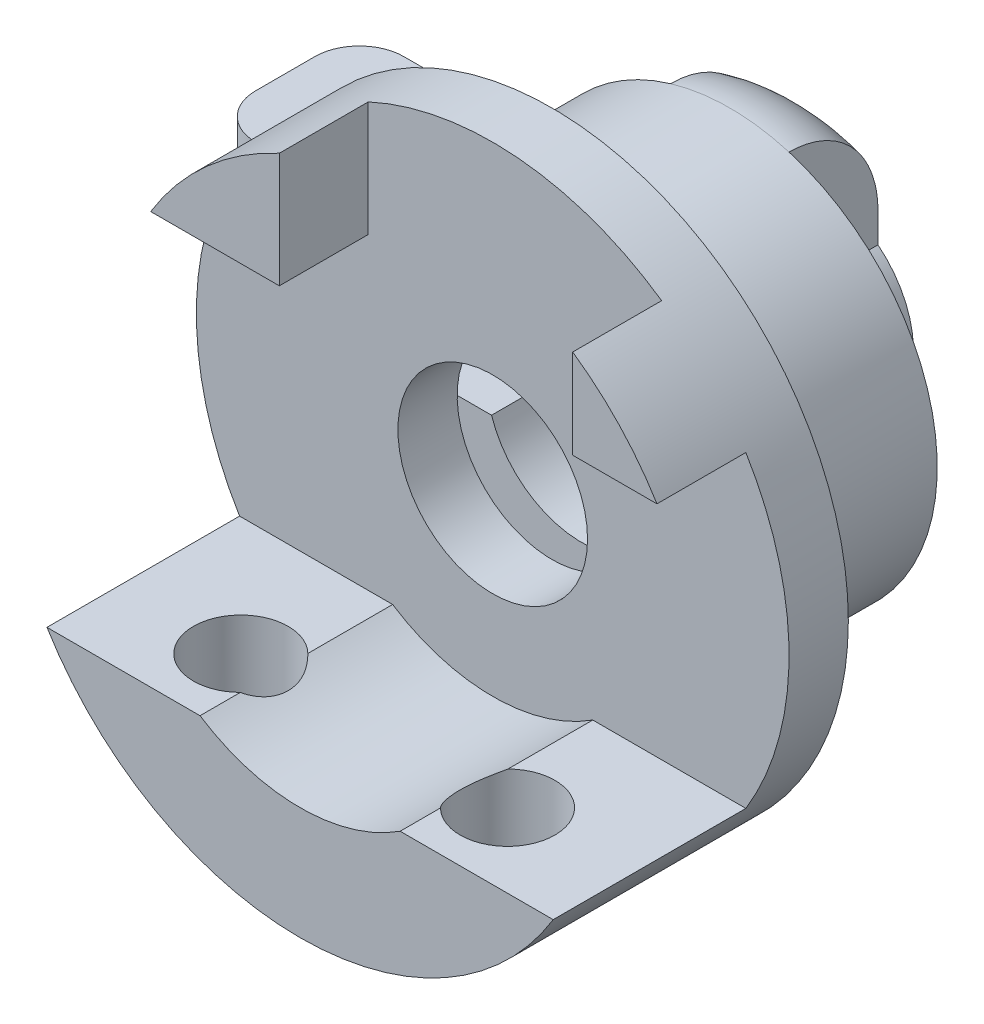
SolidWorks part; units mm, degrees
ref_plane "前视基准面" through (0, 0, 0) normal (0, 0, 1) x (1, 0, 0)
ref_plane "上视基准面" through (0, 0, 0) normal (0, 1, 0) x (1, 0, 0)
ref_plane "右视基准面" through (0, 0, 0) normal (1, 0, 0) x (0, 0, -1)
sketch "草图1" plane through (0, 0, 0) normal (0, 0, 1) x (1, 0, 0)
  circle A0 centre (0, 0) radius 10
extrude "凸台-拉伸1" add sketch "草图1" along normal blind 2
sketch "草图2" plane through (0, 0, 2) normal (0, 0, 1) x (1, 0, 0)
  line L0 (3.3764, -5.2) -> (8.5417, -5.2)
  line L1 (-4.2, 5.2) -> (-8.5417, 5.2)
  line L2 (-3.3764, -5.2) -> (-8.5417, -5.2)
  line L3 (-4.2, 5.2) -> (-4.2, 9.0752)
  line L4 (5.7, 5.2) -> (8.5417, 5.2)
  line L5 (5.7, 5.2) -> (5.7, 8.2164)
  circle A0 centre (0, 0) radius 10 construction
  arc A2 (-3.3764, -5.2) -> (3.3764, -5.2) centre (0, 0) ccw
  arc A4 (-4.2, 9.0752) -> (-8.5417, 5.2) centre (0, 0) ccw
  arc A5 (5.7, 8.2164) -> (8.5417, 5.2) centre (0, 0) cw
  arc A6 (-8.5417, -5.2) -> (-4.3589, -9) centre (0, 0) ccw
  arc A7 (8.5417, -5.2) -> (3.5784, -9.3378) centre (0, 0) cw
  arc A8 (-4.3589, -9) -> (3.5784, -9.3378) centre (0, 0) ccw
  point P3 (0, 0)
extrude "凸台-拉伸2" add sketch "草图2" along normal blind 3
sketch "草图3" plane through (0, 0, 2) normal (0, 0, 1) x (1, 0, 0)
  circle A0 centre (0, 0) radius 3.2
extrude "切除-拉伸1" cut sketch "草图3" against normal blind 3
sketch "草图5" plane through (0, 0, 0) normal (0, 0, -1) x (-1, 0, 0)
  line L0 (-3.5, 6.0622) -> (-3.5, 3.2)
  line L1 (-3.5, 3.2) -> (3.5, 3.2)
  line L5 (3.5, 6.0622) -> (3.5, 3.2)
  arc A1 (-3.5, 6.0622) -> (3.5, 6.0622) centre (0, 0) cw
  point P8 (0, 3.2)
extrude "凸台-拉伸3" add sketch "草图5" along normal blind 1
sketch "草图6" plane through (0, 0, -1) normal (0, 0, -1) x (-1, 0, 0)
  circle A0 centre (0, 0) radius 3.2
  circle A2 centre (0, 0) radius 7
extrude "凸台-拉伸4" add sketch "草图6" along normal blind 5
sketch "草图7" plane through (0, 0, -6) normal (0, 0, -1) x (-1, 0, 0)
  line L4 (12.5, -3) -> (12.5, 3)
  line L5 (4.4372, 3) -> (4.4372, -3)
  line L6 (12.5, 3) -> (4.4372, 3)
  line L7 (12.5, -3) -> (4.4372, -3)
extrude "凸台-拉伸5" add sketch "草图7" against normal blind 5
sketch "草图8" plane through (0, 3, 0) normal (0, 1, 0) x (1, 0, 0)
  circle A0 centre (-9.5, 3.5) radius 1.5
extrude "切除-拉伸3" cut sketch "草图8" against normal through all
sketch "草图9" plane through (0, 0, -6) normal (0, 0, -1) x (-1, 0, 0)
  line L0 (0, 0) -> (0, 1)
  line L1 (0, 1) -> (12.5, 1)
  line L2 (12.5, -3) -> (12.5, 3) construction
  line L3 (0, 0) -> (0, -1)
  line L4 (0, -1) -> (12.5, -1)
  line L5 (12.5, -1) -> (12.5, 1)
extrude "切除-拉伸4" cut sketch "草图9" against normal blind 5
fillet "圆角7" radius 1.5 4 edges at (-12.5, -2, -6) (-12.5, -2, -1) (-12.5, 2, -1) (-12.5, 2, -6)
sketch "草图10" plane through (0, 0, -6) normal (0, 0, -1) x (-1, 0, 0)
  line L5 (2, 6.7082) -> (2, 2.498)
  line L6 (-2, 6.7082) -> (-2, 2.498)
  arc A0 (-2, 2.498) -> (2, 2.498) centre (0, 0) cw
  circle A1 centre (0, 0) radius 3.2 construction
  arc A2 (2, 6.7082) -> (-2, 6.7082) centre (0, 0) ccw
  arc A3 (3.5, 6.0622) -> (-3.5, 6.0622) centre (0, 0) ccw construction
extrude "凸台-拉伸6" add sketch "草图10" along normal blind 3
sketch "草图12" plane through (0, 0, -9) normal (0, 0, -1) x (-1, 0, 0)
  circle A0 centre (0, 0) radius 3.2
extrude "凸台-拉伸7" add sketch "草图12" against normal blind 2
fillet "圆角8" radius 3 1 edges at (0, 7, -9)
sketch "草图13" plane through (0, 0, 5) normal (0, 0, 1) x (1, 0, 0)
  line L0 (3.3764, -5.2) -> (8.5417, -5.2)
  line L1 (-3.3764, -5.2) -> (-8.5417, -5.2)
  arc A0 (3.3764, -5.2) -> (-3.3764, -5.2) centre (0, 0) cw
  arc A1 (-8.5417, -5.2) -> (8.5417, -5.2) centre (0, 0) ccw
extrude "凸台-拉伸8" add sketch "草图13" along normal blind 3.5
sketch "草图14" plane through (0, -5.2, 0) normal (0, 1, 0) x (1, 0, 0)
  circle A0 centre (4.5, -6) radius 1.6
  circle A1 centre (-4.5, -6) radius 1.6
extrude "切除-拉伸5" cut sketch "草图14" against normal through all
